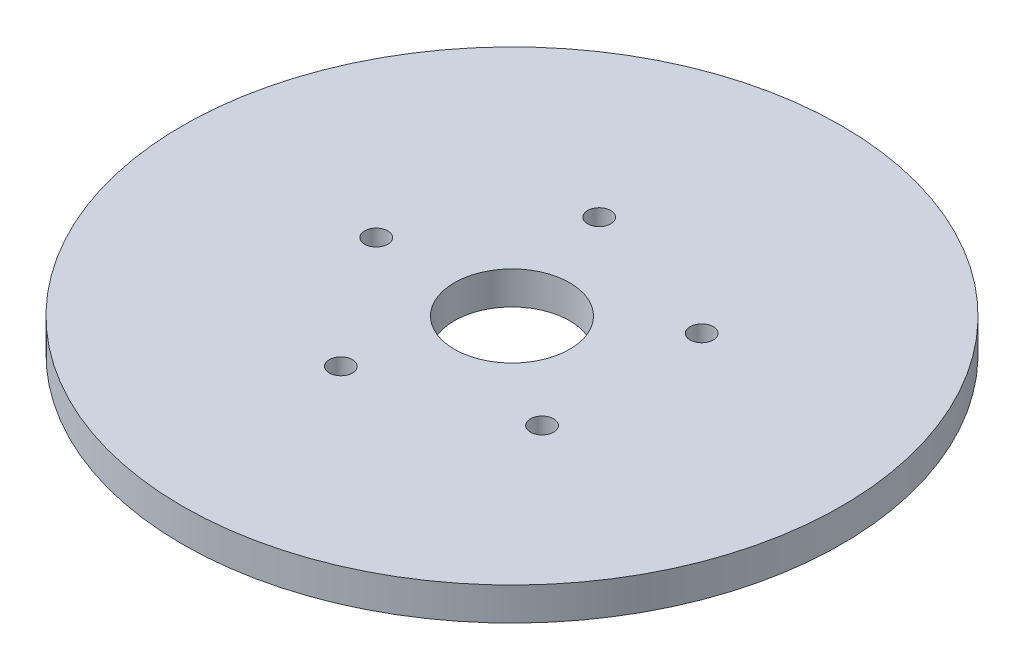
SolidWorks part; units mm, degrees
ref_plane "Front Plane" through (0, 0, 0) normal (0, 0, 1) x (1, 0, 0)
ref_plane "Top Plane" through (0, 0, 0) normal (0, 1, 0) x (1, 0, 0)
ref_plane "Right Plane" through (0, 0, 0) normal (1, 0, 0) x (0, 0, -1)
sketch "Sketch1" plane through (0, 0, 0) normal (0, 1, 0) x (1, 0, 0)
  circle A0 centre (0, 0) radius 100
  dimension "FLANGE_OD" = 200
extrude "Boss-Extrude1" add sketch "Sketch1" along normal blind 10
sketch "Sketch2" plane through (0, 0, 0) normal (0, 1, 0) x (1, 0, 0)
  circle A0 centre (0, 0) radius 17.5
  dimension "BORE_D" = 35
extrude "Cut-Extrude1" cut sketch "Sketch2" along normal through all
sketch "Sketch3" plane through (0, 10, 0) normal (0, 1, 0) x (1, 0, 0)
  circle A0 centre (0, 0) radius 41.208 construction
  circle A1 centre (-41.208, 0) radius 3.5208
  dimension "BOLT_D" = 7.0416
  dimension "BOLT_PCD" = 82.416
extrude "Cut-Extrude2" cut sketch "Sketch3" against normal blind 7.5611
pattern_circular "CirPattern1" count 5 over 360 about axis through (0, 0, 0) along (0, 1, 0) of "Cut-Extrude2"
